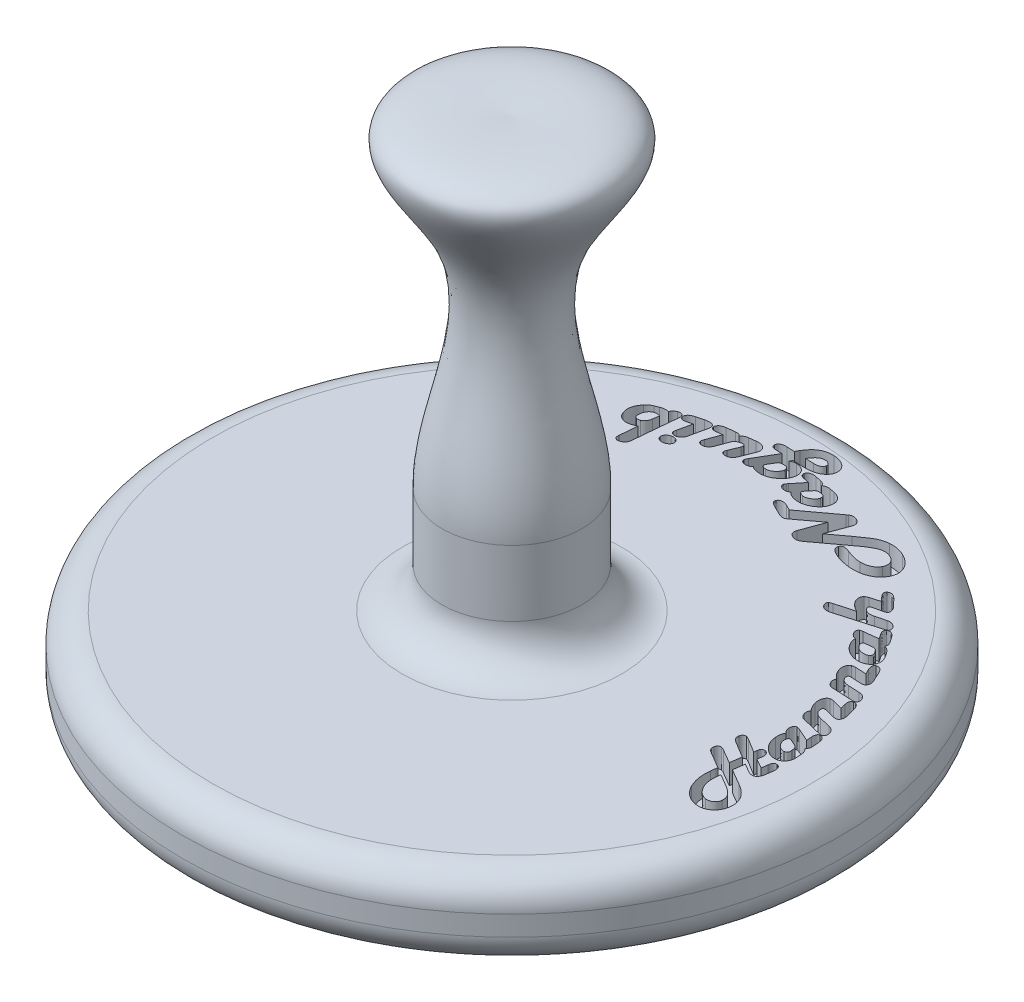
SolidWorks part; units mm, degrees
ref_plane "Front Plane" through (0, 0, 0) normal (0, 0, 1) x (1, 0, 0)
ref_plane "Top Plane" through (0, 0, 0) normal (0, 1, 0) x (1, 0, 0)
ref_plane "Right Plane" through (0, 0, 0) normal (1, 0, 0) x (0, 0, -1)
sketch "Sketch1" plane through (0, 0, 0) normal (0, 1, 0) x (1, 0, 0)
  circle A0 centre (0, 0) radius 41.91
extrude "Boss-Extrude1" add sketch "Sketch1" along normal blind 10.16
sketch "Sketch2" plane through (0, 0, 0) normal (0, 0, 1) x (1, 0, 0)
  line L0 (-8.89, 0) -> (8.89, 0)
  line L1 (-41.91, 0) -> (41.91, 0) construction
  line L2 (-8.89, 0) -> (-8.89, 10.16) construction
  line L3 (41.91, 10.16) -> (-41.91, 10.16) construction
  line L4 (8.89, 0) -> (8.89, 10.16) construction
  line L5 (0, 0) -> (0, 64.77)
  line L6 (-8.89, 10.16) -> (-8.89, 23.6119)
  line L7 (8.89, 10.16) -> (8.89, 23.6119)
  line L8 (-8.89, 10.16) -> (8.89, 10.16)
  spline S0 degree 3 poles (-8.89, 23.6119) (-9.0742, 32.2658) (2.1979, 50.6018) (-21.5553, 66.4288) (0, 64.77) knots 0 0 0 0 0.524154 1 1 1 1
  spline S1 degree 3 poles (8.89, 23.6119) (9.0742, 32.2658) (-2.1979, 50.6018) (21.5553, 66.4288) (0, 64.77) knots 0 0 0 0 0.524154 1 1 1 1
  point P7 (0, 0)
  dimension "D1" = 17.78
revolve "Revolve4" add sketch "Sketch2" angle 360 about L5 region at (-4.3936, 38.2762, 0)
fillet "Fillet2" radius 3.81 2 edges at (0, 0, 41.91) (0, 10.16, 41.91)
fillet "Fillet8" radius 5.08 1 edges at (0, 10.16, -8.89)
sketch "Sketch11" plane through (0, 10.16, 0) normal (0, 1, 0) x (1, 0, 0)
  circle A0 centre (0, 0) radius 34.4382 construction
  text T0 "annah Naguib" font "Harlow Solid Italic" height 6.35
  text T1 "                                                                                        H" font "Harlow Solid Italic" height 6.35
extrude "Cut-Extrude1" cut sketch "Sketch11" against normal blind 2.54
